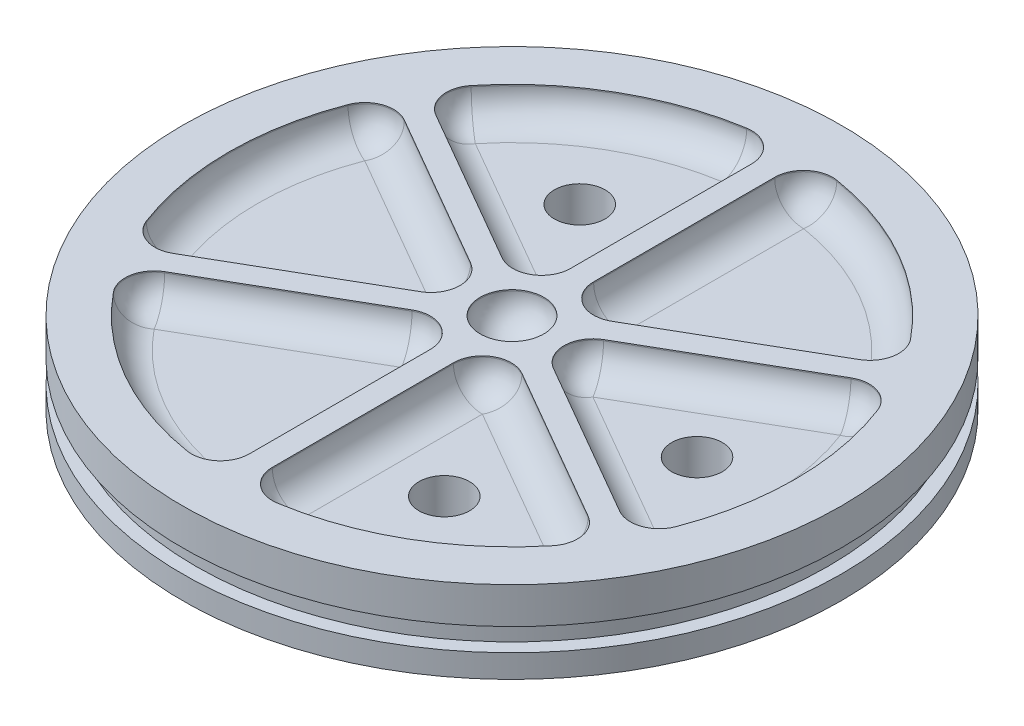
SolidWorks part; units mm, degrees
material "6061-T6 (SS)"
ref_plane "Front Plane" through (0, 0, 0) normal (0, 0, 1) x (1, 0, 0)
ref_plane "Top Plane" through (0, 0, 0) normal (0, 1, 0) x (1, 0, 0)
ref_plane "Right Plane" through (0, 0, 0) normal (1, 0, 0) x (0, 0, -1)
sketch "Sketch1" plane through (0, 0, 0) normal (0, 0, 1) x (1, 0, 0)
  line L0 (0, 48.1922) -> (0, -25.6743) construction
  line L1 (0, 0) -> (72.39, 0)
  line L2 (72.39, 0) -> (72.39, 5.08)
  line L3 (72.39, 5.08) -> (69.469, 5.08)
  line L4 (69.469, 5.08) -> (69.469, 10.0584)
  line L5 (69.469, 10.0584) -> (72.39, 10.0584)
  line L6 (72.39, 10.0584) -> (72.39, 18.034)
  line L7 (72.39, 18.034) -> (62.23, 18.034)
  line L8 (62.23, 18.034) -> (62.23, 11.43)
  line L9 (62.23, 11.43) -> (0, 11.43)
  line L10 (0, 11.43) -> (0, 0)
  dimension "D1" = 144.78
  dimension "D2" = 4.9784
  dimension "D3" = 2.921
  dimension "D5" = 11.43
  dimension "D6" = 10.16
  dimension "D4" = 18.034
  dimension "D7" = 5.08
revolve "Revolve1" add sketch "Sketch1" angle 360 about L0
sketch "Sketch6" plane through (0, 0, 0) normal (0, -1, 0) x (1, 0, 0)
  circle A0 centre (0, 0) radius 66.04
  dimension "D1" = 132.08
extrude "Boss-Extrude1" add sketch "Sketch6" along normal blind 2.54
hole_wizard "Pipe Tap Drill for 1/4 Tap - GN2" positions "Sketch2" profile "Sketch3" hole size "1/4" standard "ANSI Inch" end condition through all
sketch "Sketch2" plane through (0, 11.43, 0) normal (0, 1, 0) x (1, 0, 0)
  line L3 (-20.32, 35.1953) -> (0, 0) construction
  line L4 (0, 0) -> (40.64, 0) construction
  line L6 (0, 0) -> (20.32, -35.1953) construction
  line L7 (0, 0) -> (0, 62.23) construction
  line L8 (0, 0) -> (0, -62.23) construction
  circle A0 centre (0, 0) radius 62.23 construction
  circle A1 centre (0, 0) radius 62.23 construction
  point P41 (20.32, -35.1953)
  point P44 (-20.32, 35.1953)
  point P47 (40.64, 0)
  dimension "D1" = 40.64
  dimension "D2" = 40.64
  dimension "D3" = 40.64
  dimension "D4" = 30
  dimension "D5" = 30
sketch "Sketch3" plane through (20.32, 11.43, 35.1953) normal (1, 0, 0) x (0, 0, 1)
  line L0 (0, 0) -> (0, 13.97)
  line L1 (0, 13.97) -> (5.5626, 13.97)
  line L2 (5.5626, 13.97) -> (5.5626, 0)
  line L5 (5.5626, 0) -> (0, 0)
  line L11 (0, -6.35) -> (0, 107.95) construction
  dimension "Thru Hole Dia." = 11.1252
  dimension "Thru Hole Depth" = 13.97
fillet "CNC ID Fillet" [suppressed] radius 0.4064
fillet "CNC OD Fillet" [suppressed] radius 0.127
chamfer "CNC Chamfers" [suppressed] distance 0.508 angle 60
sketch "Sketch7" plane through (0, 18.034, 0) normal (0, 1, 0) x (1, 0, 0)
  line L0 (0, 0) -> (53.8928, -31.115) construction
  line L1 (0, 0) -> (0, -62.23) construction
  line L2 (0, 0) -> (-53.8928, -31.115) construction
  line L3 (0, 0) -> (-53.8928, 31.115) construction
  line L4 (0, 0) -> (0, 62.23) construction
  line L5 (0, 0) -> (53.8928, 31.115) construction
  line L6 (2.54, 15.3979) -> (2.54, 62.23)
  line L7 (-12.065, 9.8987) -> (-52.6228, 33.3147)
  line L8 (-14.605, -5.4993) -> (-55.1628, -28.9153)
  line L9 (-2.54, -15.3979) -> (-2.54, -62.23)
  line L10 (12.065, -9.8987) -> (52.6228, -33.3147)
  line L11 (14.605, 5.4993) -> (55.1628, 28.9153)
  line L12 (-2.54, 15.3979) -> (-2.54, 62.23)
  line L13 (-14.605, 5.4993) -> (-55.1628, 28.9153)
  line L14 (-12.065, -9.8987) -> (-52.6228, -33.3147)
  line L15 (2.54, -15.3979) -> (2.54, -62.23)
  line L16 (14.605, -5.4993) -> (55.1628, -28.9153)
  line L17 (12.065, 9.8987) -> (52.6228, 33.3147)
  line L18 (2.54, 0) -> (2.54, 62.23) construction
  line L19 (-1.27, 2.1997) -> (52.6228, 33.3147) construction
  line L20 (1.27, -2.1997) -> (55.1628, 28.9153) construction
  line L21 (1.27, 2.1997) -> (55.1628, -28.9153) construction
  line L22 (-1.27, -2.1997) -> (52.6228, -33.3147) construction
  line L23 (2.54, 0) -> (2.54, -62.23) construction
  line L24 (-2.54, 0) -> (-2.54, -62.23) construction
  line L25 (1.27, -2.1997) -> (-52.6228, -33.3147) construction
  line L26 (-1.27, 2.1997) -> (-55.1628, -28.9153) construction
  line L27 (-1.27, -2.1997) -> (-55.1628, 28.9153) construction
  line L28 (1.27, 2.1997) -> (-52.6228, 33.3147) construction
  line L29 (-2.54, 0) -> (-2.54, 62.23) construction
  line L30 (0, 0) -> (-62.23, 0) construction
  circle A0 centre (0, 0) radius 62.23 construction
  circle A1 centre (0, 0) radius 62.23
  arc A2 (2.54, 15.3979) -> (12.065, 9.8987) centre (8.89, 15.3979) ccw
  arc A3 (14.605, 5.4993) -> (14.605, -5.4993) centre (17.78, 0) ccw
  arc A4 (12.065, -9.8987) -> (2.54, -15.3979) centre (8.89, -15.3979) ccw
  arc A5 (-2.54, -15.3979) -> (-12.065, -9.8987) centre (-8.89, -15.3979) ccw
  arc A6 (-14.605, -5.4993) -> (-14.605, 5.4993) centre (-17.78, 0) ccw
  arc A7 (-12.065, 9.8987) -> (-2.54, 15.3979) centre (-8.89, 15.3979) ccw
  circle A9 centre (0, 0) radius 6.985
  point P11 (0, 0)
  circle M5 centre (0, 0) radius 62.23
  dimension "D4" = 6.35
  dimension "D6" = 13.97
  dimension "D5" = 30
  dimension "D2" = 2.54
  dimension "D3" = 2.54
  dimension "D1" = 6
extrude "Boss-Extrude2" add sketch "Sketch7" against normal up to surface (6.604 mm away) contours A7 L7 L13 A6 L8 L14 A5 L9 L15 A4 L10 L16 A3 L11 L17 A2 L6 L12 M5 region at (4.8837, 18.034, -8.4588) up to face at (20.32, 11.43, 40.7579)
fillet "Fillet1" radius 6.35 37 edges at (32.3214, 11.43, 21.5937) (5.715, 11.43, 9.8987) (34.8614, 11.43, -17.1943) (11.43, 11.43, 0) (-32.3214, 11.43, -21.5937) (-5.715, 11.43, -9.8987) (-5.715, 11.43, 9.8987) (-2.54, 11.43, 38.788) (-31.115, 11.43, 53.8928) (-32.3214, 11.43, 21.5937) (-11.43, 11.43, 0) (-34.8614, 11.43, 17.1943) (-62.23, 11.43, 0) (-34.8614, 11.43, -17.1943) (5.715, 11.43, -9.8987) (2.54, 11.43, -38.788) (31.115, 11.43, -53.8928) (32.3214, 11.43, -21.5937) (52.5779, 14.732, 33.2888) (2.54, 14.732, 62.1781) (31.115, 11.43, 53.8928) (2.54, 11.43, 38.788) (62.23, 11.43, 0) (34.8614, 11.43, 17.1943) (55.1179, 14.732, 28.8894) (55.1179, 14.732, -28.8894) (52.5779, 14.732, -33.2888) (2.54, 14.732, -62.1781) (-2.54, 14.732, 62.1781) (-52.5779, 14.732, 33.2888) (-55.1179, 14.732, 28.8894) (-52.5779, 14.732, -33.2888) (-2.54, 11.43, -38.788) (-2.54, 14.732, -62.1781) (-31.115, 11.43, -53.8928) (-55.1179, 14.732, -28.8894) (6.985, 11.43, 0)
sketch "Sketch8" plane through (0, -2.54, 0) normal (0, -1, 0) x (1, 0, 0)
  line L2 (-49.0472, -25.3844) -> (-14.605, -5.4993)
  line L3 (-14.605, 5.4993) -> (-49.0472, 25.3844)
  line L4 (-49.0472, -25.3844) -> (-14.605, -5.4993)
  line L5 (-14.605, 5.4993) -> (-49.0472, 25.3844)
  line L6 (-2.54, 15.3979) -> (-2.54, 55.1683)
  line L7 (-46.5072, 29.7839) -> (-12.065, 9.8987)
  line L8 (-2.54, 15.3979) -> (-2.54, 55.1683)
  line L9 (-46.5072, 29.7839) -> (-12.065, 9.8987)
  line L10 (12.065, 9.8987) -> (46.5072, 29.7839)
  line L11 (2.54, 55.1683) -> (2.54, 15.3979)
  line L12 (12.065, 9.8987) -> (46.5072, 29.7839)
  line L13 (2.54, 55.1683) -> (2.54, 15.3979)
  line L14 (14.605, -5.4993) -> (49.0472, -25.3844)
  line L15 (49.0472, 25.3844) -> (14.605, 5.4993)
  line L16 (14.605, -5.4993) -> (49.0472, -25.3844)
  line L17 (49.0472, 25.3844) -> (14.605, 5.4993)
  line L18 (2.54, -15.3979) -> (2.54, -55.1683)
  line L19 (46.5072, -29.7839) -> (12.065, -9.8987)
  line L20 (2.54, -15.3979) -> (2.54, -55.1683)
  line L21 (46.5072, -29.7839) -> (12.065, -9.8987)
  line L22 (-12.065, -9.8987) -> (-46.5072, -29.7839)
  line L23 (-2.54, -55.1683) -> (-2.54, -15.3979)
  line L24 (-12.065, -9.8987) -> (-46.5072, -29.7839)
  line L25 (-2.54, -55.1683) -> (-2.54, -15.3979)
  circle A0 centre (0, 0) radius 6.985 construction
  circle A1 centre (0, 0) radius 66.04
  circle A3 centre (0, 0) radius 6.985
  arc A6 (-58.1565, 22.1449) -> (-58.1565, -22.1449) centre (0, 0) ccw
  arc A7 (-58.1565, -22.1449) -> (-49.0472, -25.3844) centre (-52.2222, -19.8852) ccw
  arc A8 (-14.605, -5.4993) -> (-14.605, 5.4993) centre (-17.78, 0) ccw
  arc A9 (-49.0472, 25.3844) -> (-58.1565, 22.1449) centre (-52.2222, 19.8852) ccw
  arc A10 (-58.1565, 22.1449) -> (-58.1565, -22.1449) centre (0, 0) ccw
  arc A11 (-58.1565, -22.1449) -> (-49.0472, -25.3844) centre (-52.2222, -19.8852) ccw
  arc A12 (-14.605, -5.4993) -> (-14.605, 5.4993) centre (-17.78, 0) ccw
  arc A13 (-49.0472, 25.3844) -> (-58.1565, 22.1449) centre (-52.2222, 19.8852) ccw
  arc A14 (-2.54, 55.1683) -> (-9.9002, 61.4374) centre (-8.89, 55.1683) ccw
  arc A15 (-9.9002, 61.4374) -> (-48.2563, 39.2926) centre (0, 0) ccw
  arc A16 (-48.2563, 39.2926) -> (-46.5072, 29.7839) centre (-43.3322, 35.2831) ccw
  arc A17 (-12.065, 9.8987) -> (-2.54, 15.3979) centre (-8.89, 15.3979) ccw
  arc A18 (-2.54, 55.1683) -> (-9.9002, 61.4374) centre (-8.89, 55.1683) ccw
  arc A19 (-9.9002, 61.4374) -> (-48.2563, 39.2926) centre (0, 0) ccw
  arc A20 (-48.2563, 39.2926) -> (-46.5072, 29.7839) centre (-43.3322, 35.2831) ccw
  arc A21 (-12.065, 9.8987) -> (-2.54, 15.3979) centre (-8.89, 15.3979) ccw
  arc A22 (46.5072, 29.7839) -> (48.2563, 39.2926) centre (43.3322, 35.2831) ccw
  arc A23 (48.2563, 39.2926) -> (9.9002, 61.4374) centre (0, 0) ccw
  arc A24 (9.9002, 61.4374) -> (2.54, 55.1683) centre (8.89, 55.1683) ccw
  arc A25 (2.54, 15.3979) -> (12.065, 9.8987) centre (8.89, 15.3979) ccw
  arc A26 (46.5072, 29.7839) -> (48.2563, 39.2926) centre (43.3322, 35.2831) ccw
  arc A27 (48.2563, 39.2926) -> (9.9002, 61.4374) centre (0, 0) ccw
  arc A28 (9.9002, 61.4374) -> (2.54, 55.1683) centre (8.89, 55.1683) ccw
  arc A29 (2.54, 15.3979) -> (12.065, 9.8987) centre (8.89, 15.3979) ccw
  arc A30 (49.0472, -25.3844) -> (58.1565, -22.1449) centre (52.2222, -19.8852) ccw
  arc A31 (58.1565, -22.1449) -> (58.1565, 22.1449) centre (0, 0) ccw
  arc A32 (58.1565, 22.1449) -> (49.0472, 25.3844) centre (52.2222, 19.8852) ccw
  arc A33 (14.605, 5.4993) -> (14.605, -5.4993) centre (17.78, 0) ccw
  arc A34 (49.0472, -25.3844) -> (58.1565, -22.1449) centre (52.2222, -19.8852) ccw
  arc A35 (58.1565, -22.1449) -> (58.1565, 22.1449) centre (0, 0) ccw
  arc A36 (58.1565, 22.1449) -> (49.0472, 25.3844) centre (52.2222, 19.8852) ccw
  arc A37 (14.605, 5.4993) -> (14.605, -5.4993) centre (17.78, 0) ccw
  arc A38 (2.54, -55.1683) -> (9.9002, -61.4374) centre (8.89, -55.1683) ccw
  arc A39 (9.9002, -61.4374) -> (48.2563, -39.2926) centre (0, 0) ccw
  arc A40 (48.2563, -39.2926) -> (46.5072, -29.7839) centre (43.3322, -35.2831) ccw
  arc A41 (12.065, -9.8987) -> (2.54, -15.3979) centre (8.89, -15.3979) ccw
  arc A42 (2.54, -55.1683) -> (9.9002, -61.4374) centre (8.89, -55.1683) ccw
  arc A43 (9.9002, -61.4374) -> (48.2563, -39.2926) centre (0, 0) ccw
  arc A44 (48.2563, -39.2926) -> (46.5072, -29.7839) centre (43.3322, -35.2831) ccw
  arc A45 (12.065, -9.8987) -> (2.54, -15.3979) centre (8.89, -15.3979) ccw
  arc A46 (-46.5072, -29.7839) -> (-48.2563, -39.2926) centre (-43.3322, -35.2831) ccw
  arc A47 (-48.2563, -39.2926) -> (-9.9002, -61.4374) centre (0, 0) ccw
  arc A48 (-9.9002, -61.4374) -> (-2.54, -55.1683) centre (-8.89, -55.1683) ccw
  arc A49 (-2.54, -15.3979) -> (-12.065, -9.8987) centre (-8.89, -15.3979) ccw
  arc A50 (-46.5072, -29.7839) -> (-48.2563, -39.2926) centre (-43.3322, -35.2831) ccw
  arc A51 (-48.2563, -39.2926) -> (-9.9002, -61.4374) centre (0, 0) ccw
  arc A52 (-9.9002, -61.4374) -> (-2.54, -55.1683) centre (-8.89, -55.1683) ccw
  arc A53 (-2.54, -15.3979) -> (-12.065, -9.8987) centre (-8.89, -15.3979) ccw
  circle A54 centre (0, 0) radius 66.04
  dimension "D1" = 0
  dimension "D2" = 0
  dimension "D3" = 0
  dimension "D4" = 0
  dimension "D5" = 0
  dimension "D6" = 0
  dimension "D7" = 0
extrude "Cut-Extrude1" cut sketch "Sketch8" against normal blind 3.81 contours L8 A18 A19 A20 L9 A21 | A10 A11 L4 A12 L5 A13 | L24 A50 A51 A52 L25 A53 | L20 A42 A43 A44 L21 A45 | L16 A34 A35 A36 L17 A37 | L12 A26 A27 A28 L13 A29 | A3
fillet "Fillet2" radius 6.35 37 edges at (54.3499, 1.27, 25.8681) (62.23, 1.27, 0) (54.3499, 1.27, -25.8681) (31.8261, 1.27, -15.4419) (11.43, 1.27, 0) (4.7725, 1.27, 60.0024) (31.115, 1.27, 53.8928) (49.5774, 1.27, 34.1343) (29.2861, 1.27, 19.8413) (5.715, 1.27, 9.8987) (-5.715, 1.27, -9.8987) (-2.54, 1.27, -35.2831) (-4.7725, 1.27, -60.0024) (-31.115, 1.27, -53.8928) (-49.5774, 1.27, -34.1343) (29.2861, 1.27, -19.8413) (49.5774, 1.27, -34.1343) (31.115, 1.27, -53.8928) (4.7725, 1.27, -60.0024) (2.54, 1.27, -35.2831) (5.715, 1.27, -9.8987) (-29.2861, 1.27, 19.8413) (-49.5774, 1.27, 34.1343) (-31.115, 1.27, 53.8928) (-4.7725, 1.27, 60.0024) (-2.54, 1.27, 35.2831) (-5.715, 1.27, 9.8987) (-31.8261, 1.27, 15.4419) (-11.43, 1.27, 0) (-31.8261, 1.27, -15.4419) (-54.3499, 1.27, -25.8681) (-62.23, 1.27, 0) (-54.3499, 1.27, 25.8681) (31.8261, 1.27, 15.4419) (2.54, 1.27, 35.2831) (-29.2861, 1.27, -19.8413) (6.985, 1.27, 0)
sketch "Sketch9" plane through (0, 18.034, 0) normal (0, 1, 0) x (1, 0, 0)
  circle A0 centre (0, 0) radius 64.9299 construction
  text T0 "THIS SIDE IN                                                               FUEL BULKHEAD                                                                           RELEVANT EXPERIENCE                                "
sketch "Sketch11" plane through (0, 1.27, 0) normal (0, -1, 0) x (1, 0, 0)
  arc A0 (-43.7432, -35.6178) -> (-8.9743, -55.6917) centre (0, 0) ccw construction
  arc A1 (52.7176, -20.0738) -> (52.7176, 20.0738) centre (0, 0) ccw construction
  arc A2 (43.7432, 35.6178) -> (8.9743, 55.6917) centre (0, 0) ccw construction
  arc A3 (-43.7432, -35.6178) -> (-8.9743, -55.6917) centre (0, 0) ccw construction
  arc A4 (52.7176, -20.0738) -> (52.7176, 20.0738) centre (0, 0) ccw construction
  arc A5 (43.7432, 35.6178) -> (8.9743, 55.6917) centre (0, 0) ccw construction
  arc A6 (50.3438, -19.17) -> (50.3438, 19.17) centre (0, 0) ccw construction
  arc A7 (41.7736, 34.0141) -> (8.5702, 53.184) centre (0, 0) ccw construction
  arc A8 (-41.7736, -34.0141) -> (-8.5702, -53.184) centre (0, 0) ccw construction
  text T0 "FILL" font "Century Gothic" height in points 18
  text T1 "GN2" font "Century Gothic" height in points 18
  text T2 "VENT" font "Century Gothic" height in points 18
  dimension "D1" = 2.54
sketch "Sketch12" plane through (0, -2.54, 0) normal (0, -1, 0) x (1, 0, 0)
  line L0 (0, 0) -> (0, 64.9299) construction
  line L1 (1.397, 0) -> (1.397, 64.9299) construction
  circle A0 centre (0, 0) radius 64.9299 construction
  text T0 "THIS SIDE OUT" font "Century Gothic" height in points 11
  dimension "D1" = 1.397
equation "\"D3@Sketch1\"=(5.7-5.47)/2"
